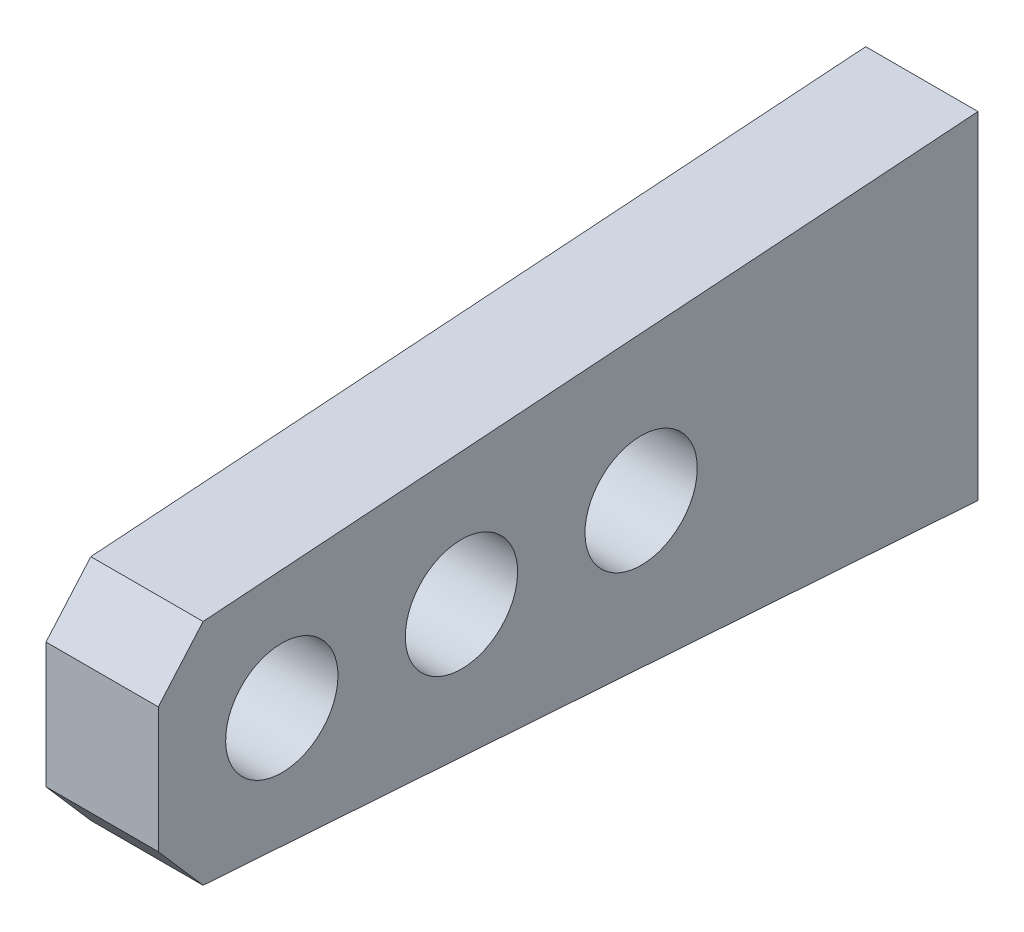
SolidWorks part; units mm, degrees
ref_plane "Plano frontal" through (0, 0, 0) normal (0, 0, 1) x (1, 0, 0)
ref_plane "Plano superior" through (0, 0, 0) normal (0, 1, 0) x (1, 0, 0)
ref_plane "Plano direito" through (0, 0, 0) normal (1, 0, 0) x (0, 0, -1)
sketch "Esboço1" plane through (0, 0, 0) normal (0, 0, 1) x (1, 0, 0)
  line L1 (-0.5, 1.5) -> (0.5, 1.5)
  line L2 (-0.5, 1.5) -> (-0.5, -1.5)
  line L3 (-0.5, -1.5) -> (0.5, -1.5)
  line L4 (0.5, 1.5) -> (0.5, -1.5)
  line L5 (-0.5, 1.5) -> (0.5, -1.5) construction
  line L6 (-0.5, -1.5) -> (0.5, 1.5) construction
  point P0 (0, 0)
  dimension "D1" = 1
  dimension "D2" = 3
extrude "Ressalto-extrusão1" add sketch "Esboço1" along normal blind 7.3
draft "Inclinação2" type of draft neutral plane draft angle 4 faces to draft 2 face at (0, 1.5, 3.65) face at (0, -1.5, 3.65) neutral plane through (0, 0, 0) neutral plane normal (0, 0, -1) reverse direction yes parameters "D1"=4
chamfer "Chanfro1" distance 0.4 angle 45 2 edges at (0, 0.9895, 7.3) (0, -0.9895, 7.3) first distance on face at (0, 1.2448, 3.65) first distance on face at (0, -1.2448, 3.65)
sketch "Esboço2" plane through (0.5, 0, 0) normal (1, 0, 0) x (0, 0, -1)
  line L0 (-7.3, 0) -> (0, 0) construction
  line L1 (-7.3, -0.5584) -> (-7.3, 0.5584) construction
  line L2 (0, -1.5) -> (0, 1.5) construction
  circle A0 centre (-6.2, 0) radius 0.5
  circle A1 centre (-4.6, 0) radius 0.5
  circle A2 centre (-3, 0) radius 0.5
  dimension "D1" = 1
  dimension "D2" = 1.6
  dimension "D3" = 1.6
  dimension "D4" = 1.1
extrude "Corte-extrusão1" cut sketch "Esboço2" against normal up to surface (1 mm away) up to face at (-0.5, 0, 4.7337)
ref_plane "Plano1" through (0, 0, 0) normal (1, 0, 0) x (0, 0, -1)
ref_axis "Eixo1" through (-0.5, 0, 6.2) along (1, 0, 0)
ref_axis "Eixo2" through (-0.5, 0, 3) along (1, 0, 0)
ref_plane "Plano2" through (0, 0, 0) normal (0, -1, 0) x (-1, 0, 0)
